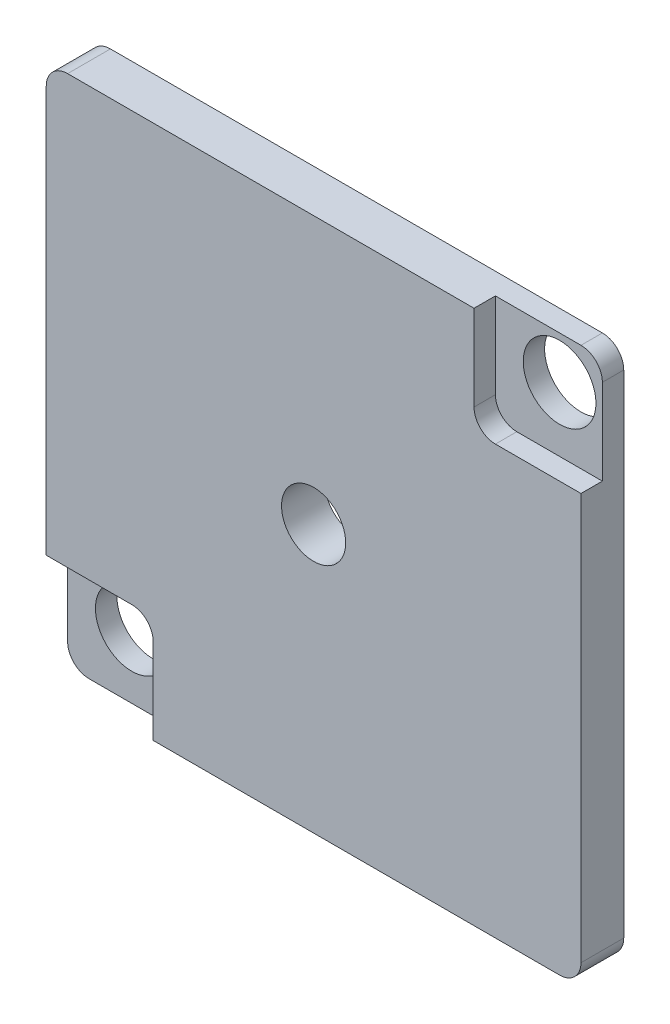
SolidWorks part; units mm, degrees
ref_plane "Front Plane" through (0, 0, 0) normal (0, 0, 1) x (1, 0, 0)
ref_plane "Top Plane" through (0, 0, 0) normal (0, 1, 0) x (1, 0, 0)
ref_plane "Right Plane" through (0, 0, 0) normal (1, 0, 0) x (0, 0, -1)
sketch "Sketch1" plane through (0, 0, 0) normal (0, 0, 1) x (1, 0, 0)
  line L0 (7.5, 12.5) -> (7.5, 8.5)
  line L1 (-12.5, 12.5) -> (12.5, 12.5)
  line L2 (-12.5, 12.5) -> (-12.5, -12.5)
  line L3 (-12.5, -12.5) -> (12.5, -12.5)
  line L4 (12.5, 12.5) -> (12.5, -12.5)
  line L5 (0, -12.5) -> (0, 12.5) construction
  line L6 (-12.5, 0) -> (12.5, 0) construction
  line L7 (8.5, 7.5) -> (12.5, 7.5)
  line L9 (-12.5, -12.5) -> (-7.5, -12.5)
  line L10 (-12.5, -12.5) -> (-12.5, -7.5)
  line L11 (-12.5, -7.5) -> (-8.5, -7.5)
  line L12 (-7.5, -12.5) -> (-7.5, -8.5)
  arc A0 (7.5, 8.5) -> (8.5, 7.5) centre (8.5, 8.5) ccw
  arc A1 (-8.5, -7.5) -> (-7.5, -8.5) centre (-8.5, -8.5) cw
  point P0 (0, 0)
  point P12 (7.5, 7.5)
  point P18 (-7.5, -7.5)
  dimension "D5" = 1
  dimension "D8" = 1
  dimension "D1" = 25
  dimension "D2" = 25
  dimension "D3" = 5
  dimension "D4" = 5
  dimension "D6" = 5
  dimension "D7" = 5
extrude "Boss-Extrude1" add sketch "Sketch1" along normal blind 1 contours L11 A1 L12 L3 L4 L7 A0 L0 L1 L2 | L0 A0 L7 L4 L1 | A1 L11 L2 L3 L12 region at (10.0197, 10.0197, 0) region at (0, 0, 0) region at (-10.0197, -10.0197, 0)
extrude "Boss-Extrude2" add sketch "Sketch1<3>" along normal blind 2 contours L11 A1 L12 L3 L4 L7 A0 L0 L1 L2 region at (0, 0, 0)
sketch "Sketch1<3>" plane through (0, 0, 0) normal (0, 0, 1) x (1, 0, 0) same geometry as "Sketch1"
fillet "Fillet1" radius 1 4 edges at (12.5, -12.5, 1) (-12.5, -12.5, 0.5) (-12.5, 12.5, 1) (12.5, 12.5, 0.5)
sketch "Sketch2" plane through (0, 0, 2) normal (0, 0, 1) x (1, 0, 0)
  circle A0 centre (0, 0) radius 1.5
  dimension "D1" = 3
extrude "Cut-Extrude1" cut sketch "Sketch2" against normal through all
hole_wizard "M3 Clearance Hole1" positions "Sketch3" profile "Sketch4" hole size "M3" standard "ISO" end condition through all
sketch "Sketch3" plane through (0, 0, 1) normal (0, 0, 1) x (1, 0, 0)
  line L0 (7.5, 12.5) -> (11.5, 12.5) construction
  line L1 (12.5, 11.5) -> (12.5, 7.5) construction
  line L2 (-8.5, -7.5) -> (-12.5, -7.5) construction
  line L3 (-7.5, -12.5) -> (-7.5, -8.5) construction
  point P0 (10.5, 10.5)
  point P2 (-9.5, -9.5)
  dimension "D1" = 2
  dimension "D2" = 2
  dimension "D3" = 2
  dimension "D4" = 2
sketch "Sketch4" plane through (10.5, 10.5, 1) normal (1, 0, 0) x (0, -1, 0)
  line L0 (0, 0) -> (0, 1)
  line L1 (0, 1) -> (1.7, 1)
  line L2 (1.7, 1) -> (1.7, 0)
  line L5 (1.7, 0) -> (0, 0)
  line L11 (0, -6.35) -> (0, 107.95) construction
  dimension "Thru Hole Dia." = 3.4
  dimension "Thru Hole Depth" = 1
